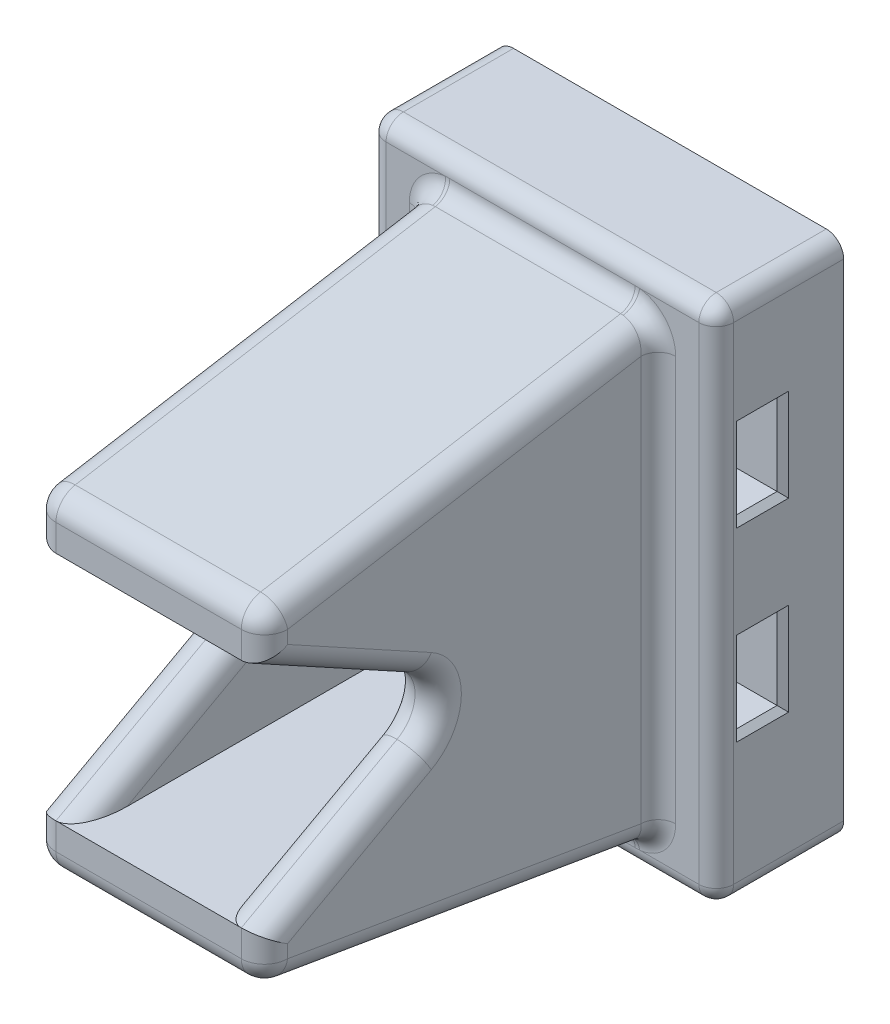
SolidWorks part; units mm, degrees
ref_plane "Спереди" through (0, 0, 0) normal (0, 0, 1) x (1, 0, 0)
ref_plane "Сверху" through (0, 0, 0) normal (0, 1, 0) x (1, 0, 0)
ref_plane "Справа" through (0, 0, 0) normal (1, 0, 0) x (0, 0, -1)
sketch "Эскиз1" plane through (0, 0, 0) normal (1, 0, 0) x (0, 0, -1)
  line L0 (0, 13.1021) -> (0, -12.6013) construction
  line L1 (-23.1444, 0) -> (19.4626, 0) construction
  line L2 (28, 22.5) -> (28, -22.5)
  line L3 (-17, -10) -> (17, -10)
  line L4 (-17, -10) -> (-17, 10)
  line L5 (-17, 10) -> (17, 10)
  line L6 (17, -10) -> (17, 10)
  line L7 (-17, -10) -> (17, 10) construction
  line L8 (-17, 10) -> (17, -10) construction
  line L9 (-17, 10) -> (-3.5578, 2.6306)
  line L10 (-17, -10) -> (-3.5578, -2.6306)
  line L11 (28, 22.5) -> (17, 22.5)
  line L12 (17, 22.5) -> (17, -22.5)
  line L13 (17, -22.5) -> (28, -22.5)
  line L14 (-17, 10) -> (-17, 14)
  line L15 (-17, 14) -> (17, 19.7538)
  line L16 (-17, -10) -> (-17, -14)
  line L17 (-17, -14) -> (17, -19.7538)
  line L18 (15.5, 25.9218) -> (15.5, -32.0814) construction
  arc A0 (-3.5578, -2.6306) -> (-3.5578, 2.6306) centre (-5, 0) ccw
  point P4 (0, 0)
  point P10 (0, 10)
  point P13 (28, 0)
  point P23 (15.5, -19.5)
  point P24 (15.5, 19.5)
  dimension "D6" = 6
  dimension "D7" = 4
  dimension "D8" = 1.5
  dimension "D1" = 20
  dimension "D2" = 34
  dimension "D3" = 11
  dimension "D4" = 45
  dimension "D5" = 12
  dimension "D9" = 3
  dimension "D10" = 3
extrude "Бобышка-Вытянуть1" add sketch "Эскиз1" along normal mid plane 30 contours L12 L13 L2 L11 L6 region at (0, 0, -22.5)
extrude "Бобышка-Вытянуть2" add sketch "Эскиз1<3>" along normal mid plane 20
sketch "Эскиз1<3>" plane through (0, 0, 0) normal (1, 0, 0) x (0, 0, -1) same geometry as "Эскиз1"
extrude "Вырез-Вытянуть1" cut sketch "Эскиз1<4>" against normal mid plane 12 contours L3 L6 L5 L9 A0 L10 | L10 A0 L9 L4 | L3 | L5 | L5 L9 | L10 L3 region at (0, 0, -3.9337) region at (0, 0, 11.2983)
sketch "Эскиз1<4>" plane through (0, 0, 0) normal (1, 0, 0) x (0, 0, -1) same geometry as "Эскиз1"
fillet "Скругление1" radius 2 22 edges at (-10, -6.3153, 10.2789) (-10, 6.3153, 10.2789) (-6, -6.3153, 10.2789) (-6, 6.3153, 10.2789) (10, -6.3153, 10.2789) (10, 6.3153, 10.2789) (6, -6.3153, 10.2789) (6, 6.3153, 10.2789) (10, -12, 17) (-10, -12, 17) (10, 12, 17) (-10, 12, 17) (-10, 0, 2) (-6, 0, 2) (10, 0, 2) (6, 0, 2) (-10, -16.8769, 0) (0, -14, 17) (10, -16.8769, 0) (0, 14, 17) (-10, 16.8769, 0) (10, 16.8769, 0)
fillet "Скругление2" radius 1.5 8 edges at (15, 0, -17) (15, -22.5, -22.5) (0, -22.5, -17) (-15, 0, -17) (-15, -22.5, -22.5) (0, 22.5, -17) (15, 22.5, -22.5) (-15, 22.5, -22.5)
fillet "Скругление3" radius 1.5 8 edges at (-9.4142, 19.1597, -17) (0, 19.7538, -17) (9.4142, 19.1597, -17) (10, 0, -17) (9.4142, -19.1597, -17) (0, -19.7538, -17) (-9.4142, -19.1597, -17) (-10, 0, -17)
sketch "Эскиз2" plane through (0, 0, -28) normal (0, 0, -1) x (-1, 0, 0)
  line L0 (0, 0) -> (0, 7.5026) construction
  line L1 (-27.9836, 0) -> (40.7692, 0) construction
  line L2 (-13.5, 22.5) -> (13.5, 22.5) construction
  line L3 (-5.5, -6.5) -> (5.5, -6.5) construction
  line L4 (-5.5, -6.5) -> (-5.5, 9.5) construction
  line L5 (-5.5, 9.5) -> (5.5, 9.5) construction
  line L6 (5.5, -6.5) -> (5.5, 9.5) construction
  line L7 (-5.5, -6.5) -> (5.5, 9.5) construction
  line L8 (-5.5, 9.5) -> (5.5, -6.5) construction
  line L9 (-7.5207, 6) -> (-15, 6)
  line L10 (-9.5415, -6.5) -> (-7.5207, -10)
  line L11 (-1.4585, 9.5) -> (-3.4793, 13)
  line L12 (-3.4793, 13) -> (-7.5207, 13)
  line L13 (-7.5207, 13) -> (-9.5415, 9.5)
  line L14 (-9.5415, 9.5) -> (-7.5207, 6)
  line L15 (-7.5207, 6) -> (-3.4793, 6)
  line L16 (-3.4793, 6) -> (-1.4585, 9.5)
  line L17 (9.5415, 9.5) -> (7.5207, 13)
  line L18 (7.5207, 13) -> (3.4793, 13)
  line L19 (3.4793, 13) -> (1.4585, 9.5)
  line L20 (1.4585, 9.5) -> (3.4793, 6)
  line L21 (3.4793, 6) -> (7.5207, 6)
  line L22 (7.5207, 6) -> (9.5415, 9.5)
  line L23 (9.5415, -6.5) -> (7.5207, -3)
  line L24 (7.5207, -3) -> (3.4793, -3)
  line L25 (3.4793, -3) -> (1.4585, -6.5)
  line L26 (1.4585, -6.5) -> (3.4793, -10)
  line L27 (3.4793, -10) -> (7.5207, -10)
  line L28 (7.5207, -10) -> (9.5415, -6.5)
  line L29 (-7.5207, -10) -> (-3.4793, -10)
  line L30 (-3.4793, -10) -> (-1.4585, -6.5)
  line L31 (-1.4585, -6.5) -> (-3.4793, -3)
  line L32 (-3.4793, -3) -> (-7.5207, -3)
  line L33 (-7.5207, -3) -> (-9.5415, -6.5)
  line L34 (-15, 21) -> (-15, -21) construction
  line L35 (-15, 6) -> (-15, 13)
  line L36 (-15, 13) -> (-7.5207, 13)
  line L37 (7.5207, 13) -> (15, 13)
  line L38 (15, 21) -> (15, -21) construction
  line L39 (15, 13) -> (15, 6)
  line L40 (15, 6) -> (7.5207, 6)
  line L41 (7.5207, -3) -> (15, -3)
  line L42 (15, -3) -> (15, -10)
  line L43 (15, -10) -> (7.5207, -10)
  line L44 (-7.5207, -3) -> (-15, -3)
  line L45 (-15, -3) -> (-15, -10)
  line L46 (-15, -10) -> (-7.5207, -10)
  circle A0 centre (-5.5, 9.5) radius 3.5 construction
  circle A1 centre (5.5, 9.5) radius 3.5 construction
  circle A2 centre (5.5, -6.5) radius 3.5 construction
  circle A3 centre (-5.5, -6.5) radius 3.5 construction
  circle A4 centre (-5.5, -6.5) radius 2.1
  circle A5 centre (-5.5, 9.5) radius 2.1
  circle A6 centre (5.5, 9.5) radius 2.1
  circle A7 centre (5.5, -6.5) radius 2.1
  point P3 (0, 1.5)
  point P6 (0, 1.5)
  line M5 (-15, 21) -> (-15, -21)
  line M9 (15, -21) -> (15, 21)
  dimension "D4" = 7
  dimension "D5" = 4.2
  dimension "D1" = 21
  dimension "D2" = 11
  dimension "D3" = 16
extrude "Вырез-Вытянуть2" cut sketch "Эскиз2" against normal mid plane 3.5 from offset 7 contours L15 L16 L11 L12 L13 L14 A5 | L36 L9 L14 L13 M5 | L21 L22 L17 L18 L19 L20 A6 | L40 L37 L17 L22 M9 | L43 L41 L23 L28 M9 | L27 L28 L23 L24 L25 L26 A7 | L32 L33 L10 L29 L30 L31 A4 | L46 L10 L33 L44 M5 region at (11.7392, -6.5, -28) region at (11.7392, 9.5, -28) region at (8.4385, 7.8035, -28) region at (5.5, -3.1069, -28) region at (-8.4385, 7.8035, -28) region at (-11.7392, 9.5, -28) region at (-11.7392, -6.5, -28) region at (-8.4385, -4.8035, -28) offset against normal yes
extrude "Вырез-Вытянуть3" cut sketch "Эскиз2<3>" against normal blind 10 contours A6 | A5 | A4 | A7 region at (5.5, -6.5, -28) region at (5.5, 9.5, -28) region at (-5.5, 9.5, -28) region at (-5.5, -6.5, -28)
sketch "Эскиз2<3>" plane through (0, 0, -28) normal (0, 0, -1) x (-1, 0, 0) same geometry as "Эскиз2"
sketch "Эскиз3" plane through (0, 0, -28) normal (0, 0, -1) x (-1, 0, 0)
  circle A0 centre (0, 0) radius 4
  circle A1 centre (0, 0) radius 2.1
  circle A2 centre (5.5, -6.5) radius 4 construction
  dimension "D1" = 8
  dimension "D2" = 4.2
  dimension "D3" = 8
extrude "Вырез-Вытянуть4" cut sketch "Эскиз3" against normal blind 5 contours A0
extrude "Вырез-Вытянуть5" cut sketch "Эскиз3<3>" against normal through all contours A1 region at (0, 0, -28)
sketch "Эскиз3<3>" plane through (0, 0, -28) normal (0, 0, -1) x (-1, 0, 0) same geometry as "Эскиз3"
chamfer "Фаска1" distance 0.5 angle 45 21 edges at (15, -6.5, -19.25) (15, -10, -21) (15, -6.5, -22.75) (15, -3, -21) (15, 6, -21) (15, 9.5, -19.25) (15, 13, -21) (15, 9.5, -22.75) (-15, 9.5, -22.75) (-15, 13, -21) (-15, 9.5, -19.25) (-15, 6, -21) (-15, -10, -21) (-15, -6.5, -22.75) (-15, -6.5, -19.25) (-15, -3, -21) (3.4, -6.5, -28) (-7.6, -6.5, -28) (-4, 0, -28) (-7.6, 9.5, -28) (3.4, 9.5, -28)
